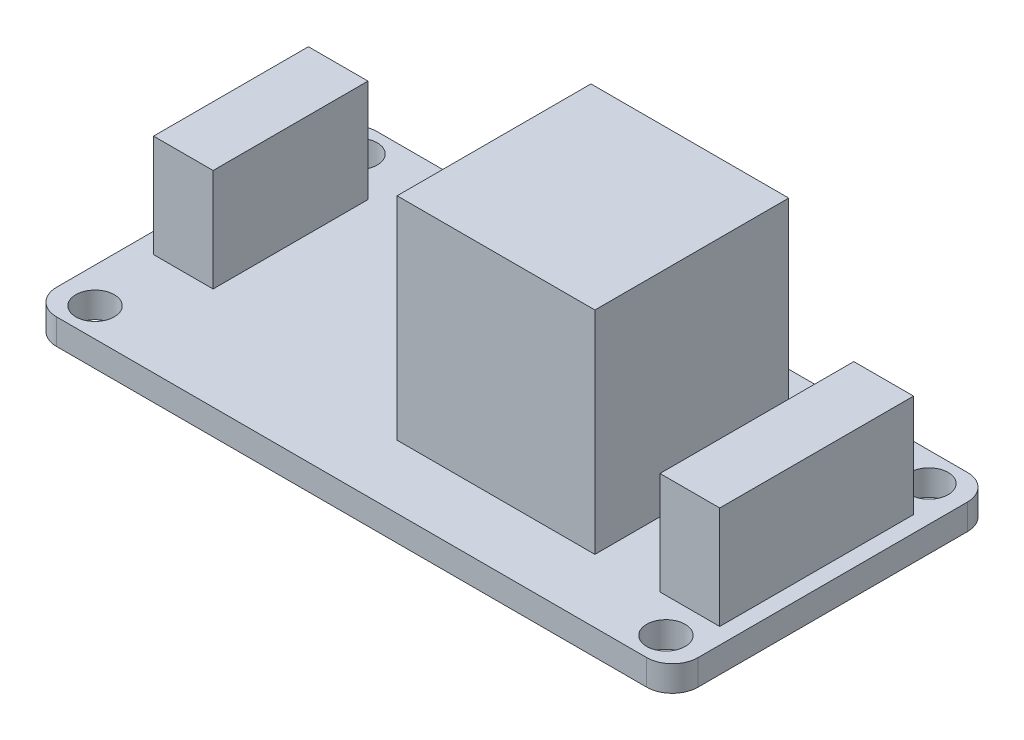
SolidWorks part; units mm, degrees
ref_plane "前视基准面" through (0, 0, 0) normal (0, 0, 1) x (1, 0, 0)
ref_plane "上视基准面" through (0, 0, 0) normal (0, 1, 0) x (1, 0, 0)
ref_plane "右视基准面" through (0, 0, 0) normal (1, 0, 0) x (0, 0, -1)
sketch "草图1" plane through (0, 0, 0) normal (0, 1, 0) x (1, 0, 0)
  line L1 (-25, -12.5) -> (25, -12.5)
  line L2 (-25, -12.5) -> (-25, 12.5)
  line L3 (-25, 12.5) -> (25, 12.5)
  line L4 (25, -12.5) -> (25, 12.5)
  line L5 (-25, -12.5) -> (25, 12.5) construction
  line L6 (-25, 12.5) -> (25, -12.5) construction
  point P0 (0, 0)
  dimension "D1" = 25
  dimension "0" = 50
extrude "凸台-拉伸1" add sketch "草图1" along normal blind 2
sketch "草图2" plane through (0, 2, 0) normal (0, 1, 0) x (1, 0, 0)
  line L1 (-1.4005, -7.5537) -> (14.0161, -7.5537)
  line L2 (-1.4005, -7.5537) -> (-1.4005, 7.5537)
  line L3 (-1.4005, 7.5537) -> (14.0161, 7.5537)
  line L4 (14.0161, -7.5537) -> (14.0161, 7.5537)
  line L5 (-1.4005, -7.5537) -> (14.0161, 7.5537) construction
  line L6 (-1.4005, 7.5537) -> (14.0161, -7.5537) construction
  line L7 (19.0897, -7.5537) -> (23.7468, -7.5537)
  line L8 (19.0897, -7.5537) -> (19.0897, 7.5537)
  line L9 (19.0897, 7.5537) -> (23.7468, 7.5537)
  line L10 (23.7468, -7.5537) -> (23.7468, 7.5537)
  line L11 (19.0897, -7.5537) -> (23.7468, 7.5537) construction
  line L12 (19.0897, 7.5537) -> (23.7468, -7.5537) construction
  line L13 (-23.4226, -4.5172) -> (-18.7798, -4.5172)
  line L14 (-23.4226, -4.5172) -> (-23.4226, 7.5537)
  line L15 (-23.4226, 7.5537) -> (-18.7798, 7.5537)
  line L16 (-18.7798, -4.5172) -> (-18.7798, 7.5537)
  line L17 (-23.4226, -4.5172) -> (-18.7798, 7.5537) construction
  line L18 (-23.4226, 7.5537) -> (-18.7798, -4.5172) construction
  point P0 (6.3078, 0)
  point P5 (21.4183, 0)
  point P10 (-21.1012, 1.5182)
extrude "凸台-拉伸2" add sketch "草图2" along normal blind 16.5 contours L2 L1 L4 L3
extrude "凸台-拉伸3" add sketch "草图2<6>" along normal blind 8 contours L13 L16 L15 L14 | L7 L10 L9 L8 region at (21.4183, 2, 0) region at (-21.1012, 2, -1.5182)
sketch "草图2<6>" plane through (0, 2, 0) normal (0, 1, 0) x (1, 0, 0) same geometry as "草图2"
sketch "草图3" plane through (0, 2, 0) normal (0, 1, 0) x (1, 0, 0)
  line L3 (0, 0) -> (0, 25.8627) construction
  line L4 (-35.6889, 0) -> (35.6889, 0) construction
  circle A0 centre (-22.25, 10.25) radius 1.5
  circle A1 centre (22.25, 10.25) radius 1.5
  circle A2 centre (22.25, -10.25) radius 1.5
  circle A3 centre (-22.25, -10.25) radius 1.5
  dimension "D1" = 3
  dimension "D2" = 44.5
  dimension "D3" = 20.5
extrude "切除-拉伸1" cut sketch "草图3" against normal through all
fillet "圆角1" radius 2 4 edges at (25, 1, -12.5) (25, 1, 12.5) (-25, 1, 12.5) (-25, 1, -12.5)
